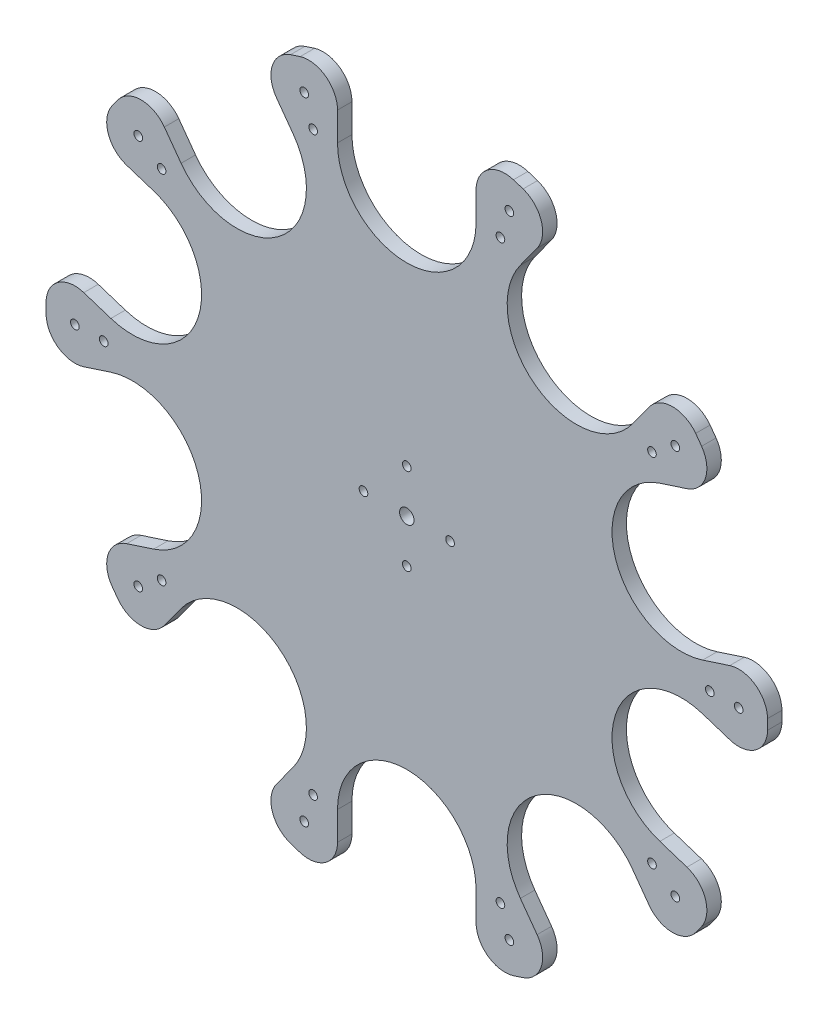
SolidWorks part; units mm, degrees
ref_plane "前视基准面" through (0, 0, 0) normal (0, 0, 1) x (1, 0, 0)
ref_plane "上视基准面" through (0, 0, 0) normal (0, 1, 0) x (1, 0, 0)
ref_plane "右视基准面" through (0, 0, 0) normal (1, 0, 0) x (0, 0, -1)
sketch "草图1" plane through (0, 0, 0) normal (0, 0, 1) x (1, 0, 0)
  line L20 (-45.1571, 102.9846) -> (-39.3621, 95.0085)
  line L21 (-78.1949, 66.7949) -> (-83.9899, 74.771)
  line L22 (-97.0657, 56.7737) -> (-87.6892, 53.7271)
  line L23 (-102.5221, 8.0763) -> (-111.8985, 11.1229)
  line L24 (-111.8985, -11.1229) -> (-102.5221, -8.0763)
  line L25 (-87.6892, -53.7271) -> (-97.0657, -56.7737)
  line L26 (-83.9899, -74.771) -> (-78.1949, -66.7949)
  line L27 (-39.3621, -95.0085) -> (-45.1571, -102.9846)
  line L28 (-24, -109.859) -> (-24, -100)
  line L29 (24, -100) -> (24, -109.859)
  line L30 (45.1571, -102.9846) -> (39.3621, -95.0085)
  line L31 (78.1949, -66.7949) -> (83.9899, -74.771)
  line L32 (97.0657, -56.7737) -> (87.6892, -53.7271)
  line L33 (102.5221, -8.0763) -> (111.8985, -11.1229)
  line L34 (111.8985, 11.1229) -> (102.5221, 8.0763)
  line L35 (87.6892, 53.7271) -> (97.0657, 56.7737)
  line L36 (83.9899, 74.771) -> (78.1949, 66.7949)
  line L37 (39.3621, 95.0085) -> (45.1571, 102.9846)
  line L38 (24, 109.859) -> (24, 100)
  line L39 (-24, 100) -> (-24, 109.859)
  line L40 (-45.1571, 102.9846) -> (-39.3621, 95.0085)
  line L41 (-78.1949, 66.7949) -> (-83.9899, 74.771)
  line L42 (-97.0657, 56.7737) -> (-87.6892, 53.7271)
  line L43 (-102.5221, 8.0763) -> (-111.8985, 11.1229)
  line L44 (-111.8985, -11.1229) -> (-102.5221, -8.0763)
  line L45 (-87.6892, -53.7271) -> (-97.0657, -56.7737)
  line L46 (-83.9899, -74.771) -> (-78.1949, -66.7949)
  line L47 (-39.3621, -95.0085) -> (-45.1571, -102.9846)
  line L48 (-24, -109.859) -> (-24, -100)
  line L49 (24, -100) -> (24, -109.859)
  line L50 (45.1571, -102.9846) -> (39.3621, -95.0085)
  line L51 (78.1949, -66.7949) -> (83.9899, -74.771)
  line L52 (97.0657, -56.7737) -> (87.6892, -53.7271)
  line L53 (102.5221, -8.0763) -> (111.8985, -11.1229)
  line L54 (111.8985, 11.1229) -> (102.5221, 8.0763)
  line L55 (87.6892, 53.7271) -> (97.0657, 56.7737)
  line L56 (83.9899, 74.771) -> (78.1949, 66.7949)
  line L57 (39.3621, 95.0085) -> (45.1571, 102.9846)
  line L58 (24, 109.859) -> (24, 100)
  line L59 (-24, 100) -> (-24, 109.859)
  arc A0 (-105, 1.5) -> (-105, -1.5) centre (-105, 0) ccw construction
  arc A1 (-105, -1.5) -> (-105, 1.5) centre (-105, 0) ccw construction
  arc A2 (-115, 1.5) -> (-115, -1.5) centre (-115, 0) ccw construction
  arc A3 (-115, -1.5) -> (-115, 1.5) centre (-115, 0) ccw construction
  arc A4 (-105, 1.5) -> (-105, -1.5) centre (-105, 0) ccw
  arc A5 (-105, -1.5) -> (-105, 1.5) centre (-105, 0) ccw
  arc A6 (-115, 1.5) -> (-115, -1.5) centre (-115, 0) ccw
  arc A7 (-115, -1.5) -> (-115, 1.5) centre (-115, 0) ccw
  arc A8 (0, 2.5) -> (0, -2.5) centre (0, 0) ccw construction
  arc A9 (0, -2.5) -> (0, 2.5) centre (0, 0) ccw construction
  arc A10 (0, 2.5) -> (0, -2.5) centre (0, 0) ccw
  arc A11 (0, -2.5) -> (0, 2.5) centre (0, 0) ccw
  arc A12 (-84.0651, 62.931) -> (-85.8285, 60.5039) centre (-84.9468, 61.7175) ccw
  arc A13 (-85.8285, 60.5039) -> (-84.0651, 62.931) centre (-84.9468, 61.7175) ccw
  arc A14 (-92.1553, 68.8088) -> (-93.9186, 66.3818) centre (-93.037, 67.5953) ccw
  arc A15 (-93.9186, 66.3818) -> (-92.1553, 68.8088) centre (-93.037, 67.5953) ccw
  arc A16 (-31.0202, 100.3245) -> (-33.8734, 99.3974) centre (-32.4468, 99.8609) ccw
  arc A17 (-33.8734, 99.3974) -> (-31.0202, 100.3245) centre (-32.4468, 99.8609) ccw
  arc A18 (-34.1104, 109.835) -> (-36.9635, 108.908) centre (-35.537, 109.3715) ccw
  arc A19 (-36.9635, 108.908) -> (-34.1104, 109.835) centre (-35.537, 109.3715) ccw
  arc A20 (33.8734, 99.3974) -> (31.0202, 100.3245) centre (32.4468, 99.8609) ccw
  arc A21 (31.0202, 100.3245) -> (33.8734, 99.3974) centre (32.4468, 99.8609) ccw
  arc A22 (36.9635, 108.908) -> (34.1104, 109.835) centre (35.537, 109.3715) ccw
  arc A23 (34.1104, 109.835) -> (36.9635, 108.908) centre (35.537, 109.3715) ccw
  arc A24 (85.8285, 60.5039) -> (84.0651, 62.931) centre (84.9468, 61.7175) ccw
  arc A25 (84.0651, 62.931) -> (85.8285, 60.5039) centre (84.9468, 61.7175) ccw
  arc A26 (93.9186, 66.3818) -> (92.1553, 68.8088) centre (93.037, 67.5953) ccw
  arc A27 (92.1553, 68.8088) -> (93.9186, 66.3818) centre (93.037, 67.5953) ccw
  arc A28 (105, -1.5) -> (105, 1.5) centre (105, 0) ccw
  arc A29 (105, 1.5) -> (105, -1.5) centre (105, 0) ccw
  arc A30 (115, -1.5) -> (115, 1.5) centre (115, 0) ccw
  arc A31 (115, 1.5) -> (115, -1.5) centre (115, 0) ccw
  arc A32 (84.0651, -62.931) -> (85.8285, -60.5039) centre (84.9468, -61.7175) ccw
  arc A33 (85.8285, -60.5039) -> (84.0651, -62.931) centre (84.9468, -61.7175) ccw
  arc A34 (92.1553, -68.8088) -> (93.9186, -66.3818) centre (93.037, -67.5953) ccw
  arc A35 (93.9186, -66.3818) -> (92.1553, -68.8088) centre (93.037, -67.5953) ccw
  arc A36 (31.0202, -100.3245) -> (33.8734, -99.3974) centre (32.4468, -99.8609) ccw
  arc A37 (33.8734, -99.3974) -> (31.0202, -100.3245) centre (32.4468, -99.8609) ccw
  arc A38 (34.1104, -109.835) -> (36.9635, -108.908) centre (35.537, -109.3715) ccw
  arc A39 (36.9635, -108.908) -> (34.1104, -109.835) centre (35.537, -109.3715) ccw
  arc A40 (-33.8734, -99.3974) -> (-31.0202, -100.3245) centre (-32.4468, -99.8609) ccw
  arc A41 (-31.0202, -100.3245) -> (-33.8734, -99.3974) centre (-32.4468, -99.8609) ccw
  arc A42 (-36.9635, -108.908) -> (-34.1104, -109.835) centre (-35.537, -109.3715) ccw
  arc A43 (-34.1104, -109.835) -> (-36.9635, -108.908) centre (-35.537, -109.3715) ccw
  arc A44 (-85.8285, -60.5039) -> (-84.0651, -62.931) centre (-84.9468, -61.7175) ccw
  arc A45 (-84.0651, -62.931) -> (-85.8285, -60.5039) centre (-84.9468, -61.7175) ccw
  arc A46 (-93.9186, -66.3818) -> (-92.1553, -68.8088) centre (-93.037, -67.5953) ccw
  arc A47 (-92.1553, -68.8088) -> (-93.9186, -66.3818) centre (-93.037, -67.5953) ccw
  arc A48 (0, 13.5) -> (0, 16.5) centre (0, 15) ccw construction
  arc A49 (0, 16.5) -> (0, 13.5) centre (0, 15) ccw construction
  arc A50 (-15, -1.5) -> (-15, 1.5) centre (-15, 0) ccw construction
  arc A51 (-36.9565, 119.412) -> (-40.2901, 118.3288) centre (0, 0) ccw
  arc A52 (-40.2901, 118.3288) -> (-45.1571, 102.9846) centre (-37.0669, 108.8625) ccw
  arc A53 (-78.1949, 66.7949) -> (-39.3621, 95.0085) centre (-58.7785, 80.9017) ccw
  arc A54 (-83.9899, 74.771) -> (-92.0801, 78.8931) centre (-92.0801, 68.8931) ccw
  arc A55 (-92.0801, 78.8931) -> (-100.087, 74.8838) centre (-92.0801, 68.8931) ccw
  arc A56 (-100.087, 74.8838) -> (-102.1473, 72.0481) centre (0, 0) ccw
  arc A57 (-102.1473, 72.0481) -> (-97.0657, 56.7737) centre (-93.9755, 66.2842) ccw
  arc A58 (-102.5221, 8.0763) -> (-87.6892, 53.7271) centre (-95.1057, 30.9017) ccw
  arc A59 (-111.8985, 11.1229) -> (-114.9887, 11.6124) centre (-114.9887, 1.6124) ccw
  arc A60 (-114.9887, 11.6124) -> (-124.9877, 1.7526) centre (-114.9887, 1.6124) ccw
  arc A61 (-124.9877, 1.7526) -> (-124.9877, -1.7526) centre (0, 0) ccw
  arc A62 (-124.9877, -1.7526) -> (-111.8985, -11.1229) centre (-114.9887, -1.6124) ccw
  arc A63 (-95.1057, -6.9017) -> (-102.5221, -8.0763) centre (-95.1057, -30.9017) ccw
  arc A64 (-87.6892, -53.7271) -> (-95.1057, -6.9017) centre (-95.1057, -30.9017) ccw
  arc A65 (-97.0657, -56.7737) -> (-102.1473, -72.0481) centre (-93.9755, -66.2842) ccw
  arc A66 (-102.1473, -72.0481) -> (-100.087, -74.8838) centre (0, 0) ccw
  arc A67 (-100.087, -74.8838) -> (-83.9899, -74.771) centre (-92.0801, -68.8931) ccw
  arc A68 (-58.7785, -56.9017) -> (-78.1949, -66.7949) centre (-58.7785, -80.9017) ccw
  arc A69 (-39.3621, -95.0085) -> (-58.7785, -56.9017) centre (-58.7785, -80.9017) ccw
  arc A70 (-45.1571, -102.9846) -> (-40.2901, -118.3288) centre (-37.0669, -108.8625) ccw
  arc A71 (-40.2901, -118.3288) -> (-36.9565, -119.412) centre (0, 0) ccw
  arc A72 (-36.9565, -119.412) -> (-24, -109.859) centre (-34, -109.859) ccw
  arc A73 (0, -76) -> (-24, -100) centre (0, -100) ccw
  arc A74 (24, -100) -> (0, -76) centre (0, -100) ccw
  arc A75 (24, -109.859) -> (36.9565, -119.412) centre (34, -109.859) ccw
  arc A76 (36.9565, -119.412) -> (40.2901, -118.3288) centre (0, 0) ccw
  arc A77 (40.2901, -118.3288) -> (45.1571, -102.9846) centre (37.0669, -108.8625) ccw
  arc A78 (58.7785, -56.9017) -> (39.3621, -95.0085) centre (58.7785, -80.9017) ccw
  arc A79 (78.1949, -66.7949) -> (58.7785, -56.9017) centre (58.7785, -80.9017) ccw
  arc A80 (83.9899, -74.771) -> (100.087, -74.8838) centre (92.0801, -68.8931) ccw
  arc A81 (100.087, -74.8838) -> (102.1473, -72.0481) centre (0, 0) ccw
  arc A82 (102.1473, -72.0481) -> (97.0657, -56.7737) centre (93.9755, -66.2842) ccw
  arc A83 (95.1057, -6.9017) -> (87.6892, -53.7271) centre (95.1057, -30.9017) ccw
  arc A84 (102.5221, -8.0763) -> (95.1057, -6.9017) centre (95.1057, -30.9017) ccw
  arc A85 (111.8985, -11.1229) -> (124.9877, -1.7526) centre (114.9887, -1.6124) ccw
  arc A86 (124.9877, -1.7526) -> (124.9877, 1.7526) centre (0, 0) ccw
  arc A87 (124.9877, 1.7526) -> (114.9887, 11.6124) centre (114.9887, 1.6124) ccw
  arc A88 (114.9887, 11.6124) -> (111.8985, 11.1229) centre (114.9887, 1.6124) ccw
  arc A89 (87.6892, 53.7271) -> (102.5221, 8.0763) centre (95.1057, 30.9017) ccw
  arc A90 (97.0657, 56.7737) -> (102.1473, 72.0481) centre (93.9755, 66.2842) ccw
  arc A91 (102.1473, 72.0481) -> (100.087, 74.8838) centre (0, 0) ccw
  arc A92 (100.087, 74.8838) -> (92.0801, 78.8931) centre (92.0801, 68.8931) ccw
  arc A93 (92.0801, 78.8931) -> (83.9899, 74.771) centre (92.0801, 68.8931) ccw
  arc A94 (39.3621, 95.0085) -> (78.1949, 66.7949) centre (58.7785, 80.9017) ccw
  arc A95 (45.1571, 102.9846) -> (40.2901, 118.3288) centre (37.0669, 108.8625) ccw
  arc A96 (40.2901, 118.3288) -> (36.9565, 119.412) centre (0, 0) ccw
  arc A97 (36.9565, 119.412) -> (34, 119.859) centre (34, 109.859) ccw
  arc A98 (34, 119.859) -> (24, 109.859) centre (34, 109.859) ccw
  arc A99 (-24, 100) -> (24, 100) centre (0, 100) ccw
  arc A100 (-24, 109.859) -> (-34, 119.859) centre (-34, 109.859) ccw
  arc A101 (-34, 119.859) -> (-36.9565, 119.412) centre (-34, 109.859) ccw
  arc A102 (-36.9565, 119.412) -> (-40.2901, 118.3288) centre (0, 0) ccw
  arc A103 (-40.2901, 118.3288) -> (-45.1571, 102.9846) centre (-37.0669, 108.8625) ccw
  arc A104 (-78.1949, 66.7949) -> (-39.3621, 95.0085) centre (-58.7785, 80.9017) ccw
  arc A105 (-83.9899, 74.771) -> (-92.0801, 78.8931) centre (-92.0801, 68.8931) ccw
  arc A106 (-92.0801, 78.8931) -> (-100.087, 74.8838) centre (-92.0801, 68.8931) ccw
  arc A107 (-100.087, 74.8838) -> (-102.1473, 72.0481) centre (0, 0) ccw
  arc A108 (-102.1473, 72.0481) -> (-97.0657, 56.7737) centre (-93.9755, 66.2842) ccw
  arc A109 (-102.5221, 8.0763) -> (-87.6892, 53.7271) centre (-95.1057, 30.9017) ccw
  arc A110 (-111.8985, 11.1229) -> (-114.9887, 11.6124) centre (-114.9887, 1.6124) ccw
  arc A111 (-114.9887, 11.6124) -> (-124.9877, 1.7526) centre (-114.9887, 1.6124) ccw
  arc A112 (-124.9877, 1.7526) -> (-124.9877, -1.7526) centre (0, 0) ccw
  arc A113 (-124.9877, -1.7526) -> (-111.8985, -11.1229) centre (-114.9887, -1.6124) ccw
  arc A114 (-95.1057, -6.9017) -> (-102.5221, -8.0763) centre (-95.1057, -30.9017) ccw
  arc A115 (-87.6892, -53.7271) -> (-95.1057, -6.9017) centre (-95.1057, -30.9017) ccw
  arc A116 (-97.0657, -56.7737) -> (-102.1473, -72.0481) centre (-93.9755, -66.2842) ccw
  arc A117 (-102.1473, -72.0481) -> (-100.087, -74.8838) centre (0, 0) ccw
  arc A118 (-100.087, -74.8838) -> (-83.9899, -74.771) centre (-92.0801, -68.8931) ccw
  arc A119 (-58.7785, -56.9017) -> (-78.1949, -66.7949) centre (-58.7785, -80.9017) ccw
  arc A120 (-39.3621, -95.0085) -> (-58.7785, -56.9017) centre (-58.7785, -80.9017) ccw
  arc A121 (-45.1571, -102.9846) -> (-40.2901, -118.3288) centre (-37.0669, -108.8625) ccw
  arc A122 (-40.2901, -118.3288) -> (-36.9565, -119.412) centre (0, 0) ccw
  arc A123 (-36.9565, -119.412) -> (-24, -109.859) centre (-34, -109.859) ccw
  arc A124 (0, -76) -> (-24, -100) centre (0, -100) ccw
  arc A125 (24, -100) -> (0, -76) centre (0, -100) ccw
  arc A126 (24, -109.859) -> (36.9565, -119.412) centre (34, -109.859) ccw
  arc A127 (36.9565, -119.412) -> (40.2901, -118.3288) centre (0, 0) ccw
  arc A128 (40.2901, -118.3288) -> (45.1571, -102.9846) centre (37.0669, -108.8625) ccw
  arc A129 (58.7785, -56.9017) -> (39.3621, -95.0085) centre (58.7785, -80.9017) ccw
  arc A130 (78.1949, -66.7949) -> (58.7785, -56.9017) centre (58.7785, -80.9017) ccw
  arc A131 (83.9899, -74.771) -> (100.087, -74.8838) centre (92.0801, -68.8931) ccw
  arc A132 (100.087, -74.8838) -> (102.1473, -72.0481) centre (0, 0) ccw
  arc A133 (102.1473, -72.0481) -> (97.0657, -56.7737) centre (93.9755, -66.2842) ccw
  arc A134 (95.1057, -6.9017) -> (87.6892, -53.7271) centre (95.1057, -30.9017) ccw
  arc A135 (102.5221, -8.0763) -> (95.1057, -6.9017) centre (95.1057, -30.9017) ccw
  arc A136 (111.8985, -11.1229) -> (124.9877, -1.7526) centre (114.9887, -1.6124) ccw
  arc A137 (124.9877, -1.7526) -> (124.9877, 1.7526) centre (0, 0) ccw
  arc A138 (124.9877, 1.7526) -> (114.9887, 11.6124) centre (114.9887, 1.6124) ccw
  arc A139 (114.9887, 11.6124) -> (111.8985, 11.1229) centre (114.9887, 1.6124) ccw
  arc A140 (87.6892, 53.7271) -> (102.5221, 8.0763) centre (95.1057, 30.9017) ccw
  arc A141 (97.0657, 56.7737) -> (102.1473, 72.0481) centre (93.9755, 66.2842) ccw
  arc A142 (102.1473, 72.0481) -> (100.087, 74.8838) centre (0, 0) ccw
  arc A143 (100.087, 74.8838) -> (92.0801, 78.8931) centre (92.0801, 68.8931) ccw
  arc A144 (92.0801, 78.8931) -> (83.9899, 74.771) centre (92.0801, 68.8931) ccw
  arc A145 (39.3621, 95.0085) -> (78.1949, 66.7949) centre (58.7785, 80.9017) ccw
  arc A146 (45.1571, 102.9846) -> (40.2901, 118.3288) centre (37.0669, 108.8625) ccw
  arc A147 (40.2901, 118.3288) -> (36.9565, 119.412) centre (0, 0) ccw
  arc A148 (36.9565, 119.412) -> (34, 119.859) centre (34, 109.859) ccw
  arc A149 (34, 119.859) -> (24, 109.859) centre (34, 109.859) ccw
  arc A150 (-24, 100) -> (24, 100) centre (0, 100) ccw
  arc A151 (-24, 109.859) -> (-34, 119.859) centre (-34, 109.859) ccw
  arc A152 (-34, 119.859) -> (-36.9565, 119.412) centre (-34, 109.859) ccw
  arc A153 (-15, 1.5) -> (-15, -1.5) centre (-15, 0) ccw construction
  arc A154 (0, -13.5) -> (0, -16.5) centre (0, -15) ccw construction
  arc A155 (0, -16.5) -> (0, -13.5) centre (0, -15) ccw construction
  arc A156 (15, -1.5) -> (15, 1.5) centre (15, 0) ccw construction
  arc A157 (15, 1.5) -> (15, -1.5) centre (15, 0) ccw construction
  arc A158 (15, 1.5) -> (15, -1.5) centre (15, 0) ccw
  arc A159 (15, -1.5) -> (15, 1.5) centre (15, 0) ccw
  arc A160 (0, -16.5) -> (0, -13.5) centre (0, -15) ccw
  arc A161 (0, -13.5) -> (0, -16.5) centre (0, -15) ccw
  arc A162 (-15, 1.5) -> (-15, -1.5) centre (-15, 0) ccw
  arc A163 (-15, -1.5) -> (-15, 1.5) centre (-15, 0) ccw
  arc A164 (0, 16.5) -> (0, 13.5) centre (0, 15) ccw
  arc A165 (0, 13.5) -> (0, 16.5) centre (0, 15) ccw
  point P208 (0, 0)
  dimension "D1" = 0
  dimension "D2" = 10
extrude "凸台-拉伸1" add sketch "草图1" along normal blind 5
